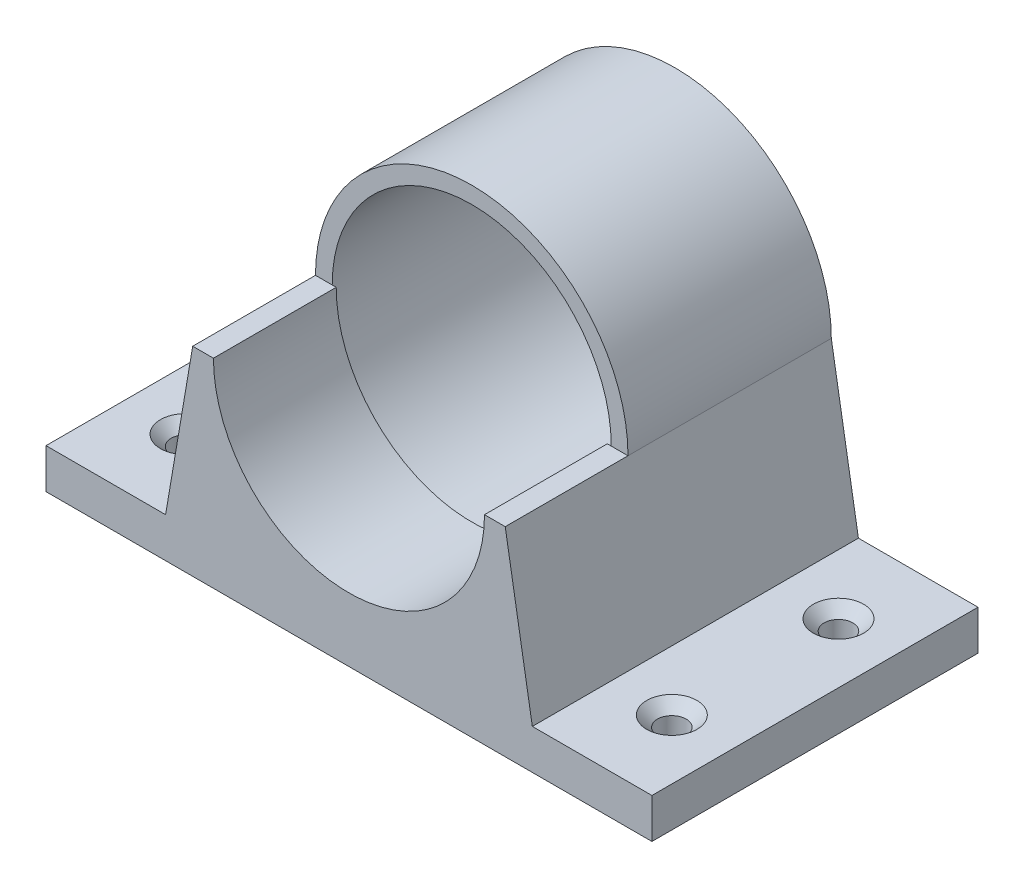
SolidWorks part; units mm, degrees
ref_plane "Front Plane" through (0, 0, 0) normal (0, 0, 1) x (1, 0, 0)
ref_plane "Top Plane" through (0, 0, 0) normal (0, 1, 0) x (1, 0, 0)
ref_plane "Right Plane" through (0, 0, 0) normal (1, 0, 0) x (0, 0, -1)
sketch "Sketch1" plane through (0, 0, 0) normal (0, 0, 1) x (1, 0, 0)
  line L0 (-23, -1.8466) -> (-38, -1.8466)
  line L6 (-38, -1.8466) -> (-38, -6.8466)
  line L7 (23, -1.8466) -> (38, -1.8466)
  line L9 (0, 0) -> (0, 18.1534)
  line L12 (38, -1.8466) -> (38, -6.8466)
  line L13 (-23, -1.8466) -> (-19.6, 18.1534)
  line L14 (19.6, 18.1534) -> (23, -1.8466)
  line L15 (-38, -6.8466) -> (38, -6.8466)
  line L16 (-19.6, 18.1534) -> (-17, 18.1534)
  line L17 (17, 18.1534) -> (19.6, 18.1534)
  circle A2 centre (0, 18.1534) radius 17.5
  arc A3 (-19.6, 18.1534) -> (19.6, 18.1534) centre (0, 18.1534) cw
  arc A4 (-19.6, 18.1534) -> (19.6, 18.1534) centre (0, 18.1534) ccw
  arc A6 (17, 18.1534) -> (-17, 18.1534) centre (0, 18.1534) cw
  dimension "D3" = 35
  dimension "D4" = 17
  dimension "D5" = 19.6
  dimension "D1" = 25
  dimension "D2" = 5
  dimension "D7" = 15
  dimension "D8" = 23
extrude "Boss-Extrude9" add sketch "Sketch1" against normal blind 25.5 contours A3 A4 | A2
extrude "Boss-Extrude10" add sketch "Sketch1<15>" against normal blind 25.5 and the other way blind 15.4 contours L13 L0 L6 L15 L12 L7 L14 A4
sketch "Sketch1<15>" plane through (0, 0, 0) normal (0, 0, 1) x (1, 0, 0) same geometry as "Sketch1"
sketch "Sketch8" plane through (0, -1.8466, 0) normal (0, 1, 0) x (1, 0, 0)
  line L0 (-30.5, -15.4) -> (-30.5, -5.4)
  line L1 (-23, -15.4) -> (-38, -15.4) construction
  line L2 (-23, 25.5) -> (-38, 25.5) construction
  line L3 (-30.5, 25.5) -> (-30.5, 15.5)
  line L4 (0, 0) -> (0, 27.9846) construction
  line L5 (30.5, -15.4) -> (30.5, -5.4)
  line L6 (30.5, 25.5) -> (30.5, 15.5)
  dimension "D1" = 10
hole_wizard "CSK for M3 Flat Head Machine Screw1" positions "Sketch11" profile "Sketch10" countersink size "M3" standard "ANSI Metric" end condition through all
sketch "Sketch11" plane through (0, -1.8466, 0) normal (0, 1, 0) x (1, 0, 0)
  point P0 (-30.5, 15.5)
  point P3 (-30.5, -5.4)
sketch "Sketch10" plane through (-30.5, -1.8466, -15.5) normal (1, 0, 0) x (0, 0, 1)
  line L0 (0, 0) -> (0, 5)
  line L1 (0, 5) -> (1.8, 5)
  line L2 (1.8, 5) -> (1.8, 1.35)
  line L3 (1.8, 1.35) -> (3.15, 0)
  line L5 (3.15, 0) -> (0, 0)
  line L6 (-1.8, 1.35) -> (-3.15, 0) construction
  line L11 (0, -6.35) -> (0, 107.95) construction
  dimension "Thru Hole Dia." = 3.6
  dimension "Thru Hole Depth" = 5
  dimension "Near C'Sink Dia." = 6.3
  dimension "Near C'Sink Angle" = 90
hole_wizard "CSK for M3 Flat Head Machine Screw2" positions "Sketch13" profile "Sketch14" countersink size "M3" standard "ANSI Metric" end condition through all
sketch "Sketch13" plane through (0, -1.8466, 0) normal (0, 1, 0) x (1, 0, 0)
  point P0 (30.5, -5.4)
  point P3 (30.5, 15.5)
sketch "Sketch14" plane through (30.5, -1.8466, 5.4) normal (1, 0, 0) x (0, 0, 1)
  line L0 (0, 0) -> (0, 5)
  line L1 (0, 5) -> (1.8, 5)
  line L2 (1.8, 5) -> (1.8, 1.35)
  line L3 (1.8, 1.35) -> (3.15, 0)
  line L5 (3.15, 0) -> (0, 0)
  line L6 (-1.8, 1.35) -> (-3.15, 0) construction
  line L11 (0, -6.35) -> (0, 107.95) construction
  dimension "Thru Hole Dia." = 3.6
  dimension "Thru Hole Depth" = 5
  dimension "Near C'Sink Dia." = 6.3
  dimension "Near C'Sink Angle" = 90
extrude "Boss-Extrude11" add sketch "Sketch1<19>" along normal blind 15.4 contours L9 A6 L16 A2 | L17 A6 L9 A2 | L16 A4 L17 A2 region at (-18.55, 17.7151, 0) region at (-17.25, 17.9059, 0) region at (12.1994, 5.954, 0)
sketch "Sketch1<19>" plane through (0, 0, 0) normal (0, 0, 1) x (1, 0, 0) same geometry as "Sketch1"
